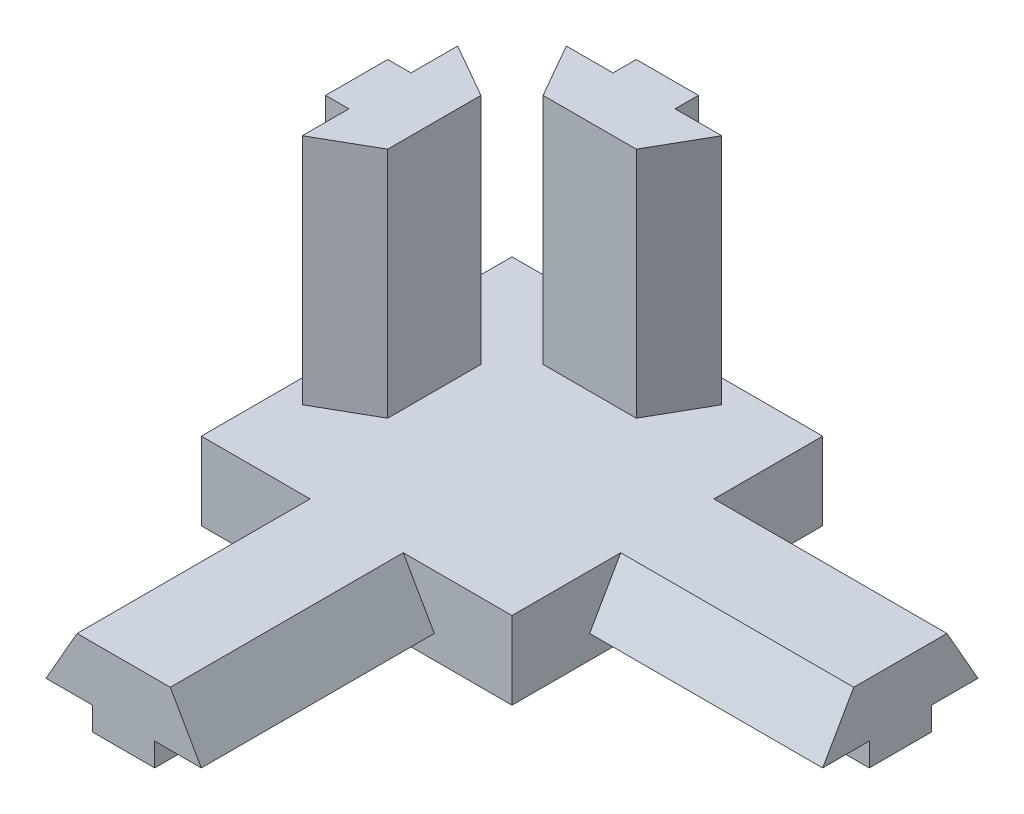
SolidWorks part; units mm, degrees
note: '?' marks a value the reader was unsure of.
ref_plane "Front" through (0, 0, 0) normal (0, 0, 1) x (1, 0, 0)
ref_plane "Top" through (0, 0, 0) normal (0, 1, 0) x (1, 0, 0)
ref_plane "Right" through (0, 0, 0) normal (1, 0, 0) x (0, 0, -1)
sketch "Sketch1" plane through (0, 0, 0) normal (0, 1, 0) x (1, 0, 0)
  line L1 (-10, -10) -> (10, -10)
  line L2 (-10, -10) -> (-10, 10)
  line L3 (-10, 10) -> (10, 10)
  line L4 (10, -10) -> (10, 10)
  line L5 (-10, -10) -> (10, 10) construction
  line L6 (-10, 10) -> (10, -10) construction
  point P0 (0, 0)
  dimension "D1" = 20
  dimension "D2" = 20
extrude "Boss-Extrude1" add sketch "Sketch1" along normal mid plane 5
sketch "Sketch2" plane through (0, 2.5, 0) normal (0, 1, 0) x (1, 0, 0)
  line L0 (-2, 10) -> (2, 10)
  line L1 (10, 10) -> (-10, 10) construction
  line L2 (2, 10) -> (2, 8.5)
  line L3 (2, 8.5) -> (5, 8.5)
  line L5 (3, 5) -> (-3, 5)
  line L7 (-5, 8.5) -> (-2, 8.5)
  line L8 (-2, 8.5) -> (-2, 10)
  line L9 (0, -50) -> (0, 50) construction
  line L10 (-5, 8.5) -> (-3, 5)
  line L11 (5, 8.5) -> (3, 5)
  point P10 (0, 5)
  point P13 (-2, 9.25)
  point P14 (0, 10)
  point P15 (2.5594, 5)
  dimension "D1" = 1.5
  dimension "D2" = 4
  dimension "D3" = 10
  dimension "D4" = 5
  dimension "D5" = 6
extrude "Boss-Extrude2" add sketch "Sketch2" along normal blind 15 contours L3 L11 L5 L10 L7 L8 L0 L2
ref_axis "Axis1" through (0, -50, 0) along (0, 1, 0)?
pattern_circular "CirPattern1" count 2 every 90 about axis through (0, 0, 0) along (0, 1, 0) of "Boss-Extrude2"
sketch "Sketch3" plane through (10, 0, 0) normal (1, 0, 0) x (0, 0, -1)
  line L0 (-3, 2.5) -> (3, 2.5)
  line L1 (3, 2.5) -> (-3, 2.5) construction
  line L2 (-10, 2.5) -> (10, 2.5) construction
  line L3 (3, 2.5) -> (5, -1)
  line L4 (5, -1) -> (2, -1)
  line L5 (2, -1) -> (2, -2.5)
  line L6 (-10, -2.5) -> (10, -2.5) construction
  line L7 (2, -2.5) -> (-2, -2.5)
  line L8 (-2, -2.5) -> (-2, -1)
  line L9 (-2, -1) -> (-5, -1)
  line L10 (-5, -1) -> (-3, 2.5)
  line L11 (0, 50) -> (0, -50) construction
  point P14 (0, -2.5)
  point P17 (0, 2.5)
  dimension "D1" = 4
  dimension "D2" = 10
  dimension "D3" = 6
  dimension "D4" = 1.5
extrude "Boss-Extrude3" add sketch "Sketch3" along normal blind 15
pattern_circular "CirPattern2" count 2 every 90 about axis through (0, 0, 0) along (0, 1, 0) of "Boss-Extrude3"
